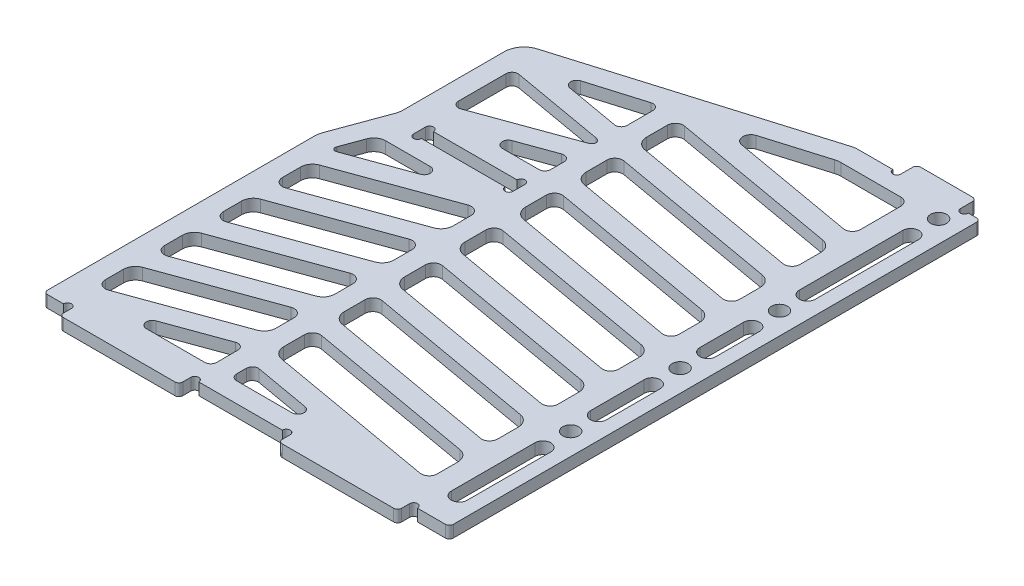
SolidWorks part; units mm, degrees
material "Thornel Mat VMA"
ref_plane "前视基准面" through (0, 0, 0) normal (0, 0, 1) x (1, 0, 0)
ref_plane "上视基准面" through (0, 0, 0) normal (0, 1, 0) x (1, 0, 0)
ref_plane "右视基准面" through (0, 0, 0) normal (1, 0, 0) x (0, 0, -1)
sketch "草图1" plane through (0, 0, 0) normal (0, 1, 0) x (1, 0, 0)
  line L0 (0, 0) -> (0, -3)
  line L1 (0, -3) -> (-30, -3)
  line L2 (-30, -3) -> (-30, 0)
  line L3 (-30, 0) -> (-55, 0)
  line L4 (-55, 0) -> (-55, -3)
  line L5 (-55, -3) -> (-85, -3)
  line L6 (-85, -3) -> (-85, 0)
  line L7 (-85, 0) -> (-92, 0)
  line L8 (-92, 0) -> (-92, 69)
  line L9 (-21.5, 133.5) -> (-10, 133.5)
  line L10 (10, 133.5) -> (10, 0)
  line L11 (10, 0) -> (0, 0)
  line L12 (5, 133.5) -> (10, 133.5)
  line L18 (5, 133.5) -> (5, 137.5)
  line L19 (5, 137.5) -> (-10, 137.5)
  line L20 (-10, 133.5) -> (-10, 137.5)
  line L22 (-86.5, 84) -> (-86.5, 114)
  line L23 (-86.5, 114) -> (-21.5, 133.5)
  line L24 (4.5, 121.5) -> (4.5, 95.5) construction
  line L25 (6.5, 121.5) -> (6.5, 95.5)
  line L26 (2.5, 121.5) -> (2.5, 95.5)
  line L27 (4.5, 81.5) -> (4.5, 70.5) construction
  line L28 (6.5, 81.5) -> (6.5, 70.5)
  line L29 (2.5, 81.5) -> (2.5, 70.5)
  line L31 (-80, 84) -> (-80, 81)
  line L33 (-80, 81) -> (-55, 81)
  line L34 (-55, 84) -> (-80, 84)
  line L37 (-55, 81) -> (-55, 84)
  line L38 (-92, 69) -> (-86.5, 84)
  line L39 (4.5, 56.5) -> (4.5, 43) construction
  line L40 (6.5, 56.5) -> (6.5, 43)
  line L41 (2.5, 56.5) -> (2.5, 43)
  line L42 (4.5, 29) -> (4.5, 8) construction
  line L43 (6.5, 29) -> (6.5, 8)
  line L44 (2.5, 29) -> (2.5, 8)
  circle A1 centre (4.5, 128.5) radius 2
  circle A5 centre (4.5, 36) radius 2
  circle A6 centre (4.5, 63.5) radius 2
  circle A7 centre (4.5, 88.5) radius 2
  arc A8 (6.5, 121.5) -> (2.5, 121.5) centre (4.5, 121.5) ccw
  arc A9 (2.5, 95.5) -> (6.5, 95.5) centre (4.5, 95.5) ccw
  arc A10 (6.5, 81.5) -> (2.5, 81.5) centre (4.5, 81.5) ccw
  arc A11 (2.5, 70.5) -> (6.5, 70.5) centre (4.5, 70.5) ccw
  arc A12 (6.5, 56.5) -> (2.5, 56.5) centre (4.5, 56.5) ccw
  arc A13 (2.5, 43) -> (6.5, 43) centre (4.5, 43) ccw
  arc A14 (6.5, 29) -> (2.5, 29) centre (4.5, 29) ccw
  arc A15 (2.5, 8) -> (6.5, 8) centre (4.5, 8) ccw
  point P28 (4.5, 108.5)
  point P41 (4.5, 76)
  point P46 (4.5, 49.75)
  point P55 (4.5, 18.5)
  point P63 (4.5, 123.5)
  point P64 (4.5, 93.5)
  point P68 (4.5, 83.5)
  point P69 (4.5, 68.5)
  point P70 (4.5, 58.5)
  point P71 (4.5, 41)
  point P72 (4.5, 31)
  point P73 (4.5, 6)
  dimension "D20" = 4
  dimension "D21" = 5
  dimension "D22" = 40
  dimension "D23" = 25
  dimension "D24" = 27.5
  dimension "D28" = 5
  dimension "D30" = 5
  dimension "D31" = 5
  dimension "D1" = 3
  dimension "D2" = 10
  dimension "D3" = 133.5
  dimension "D4" = 30
  dimension "D5" = 25
  dimension "D6" = 30
  dimension "D7" = 7
  dimension "D8" = 4
  dimension "D9" = 5
  dimension "D10" = 81
  dimension "D11" = 3
  dimension "D12" = 5.5
  dimension "D13" = 25
  dimension "D14" = 6.5
  dimension "D15" = 15
  dimension "D16" = 15
  dimension "D17" = 30
  dimension "D18" = 65
  dimension "D19" = 5.5
  dimension "D25" = 5
  dimension "D26" = 5
  dimension "D27" = 4
  dimension "D29" = 5
  dimension "D32" = 5
  dimension "D33" = 6
extrude "凸台-拉伸1" add sketch "草图1" along normal blind 3
sketch "草图3" plane through (0, 3, 0) normal (0, 1, 0) x (1, 0, 0)
  line L38 (-84.1078, 76) -> (-55, 76)
  line L39 (-81.5, 89) -> (-55, 89)
  line L40 (-55, 89) -> (-55, 118.2298)
  line L41 (-50, 119.7298) -> (-50, 5)
  line L42 (-55, 76) -> (-55, 5)
  line L43 (-80, 81) -> (-55, 81) construction
  line L44 (-55, 84) -> (-80, 84) construction
  line L45 (-55, 81) -> (-55, 84) construction
  line L46 (-55, 118.2298) -> (-81.5, 110.2798)
  line L47 (-50, 5) -> (-3, 5)
  line L48 (-3, 128.5) -> (-3, 5)
  line L49 (10, 0) -> (10, 133.5) construction
  line L57 (-5, 128.5) -> (-20.7662, 128.5)
  line L58 (-20.7662, 128.5) -> (-81.5, 110.2798)
  line L59 (-81.5, 110.2798) -> (-81.5, 83.1122)
  line L60 (-81.5, 83.1122) -> (-87, 68.1122)
  line L61 (-87, 68.1122) -> (-87, 5)
  line L62 (-87, 5) -> (-80, 5)
  line L63 (-80, 2) -> (-60, 2)
  line L64 (-60, 5) -> (-25, 5)
  line L65 (-25, 2) -> (-5, 2)
  line L66 (-5, 5) -> (5, 5)
  line L67 (5, 5) -> (5, 128.5)
  line L68 (0, 132.5) -> (-5, 132.5)
  line L69 (-3, 128.5) -> (-20.7662, 128.5)
  line L70 (-20.7662, 128.5) -> (-50, 119.7298)
  line L71 (-81.5, 110.2798) -> (-81.5, 89)
  line L72 (-84.1078, 76) -> (-87, 68.1122)
  line L73 (-87, 68.1122) -> (-87, 5)
  line L76 (-87, 5) -> (-55, 5)
  line L81 (-80, 5) -> (-80, 2)
  line L83 (-60, 2) -> (-60, 5)
  line L85 (-25, 5) -> (-25, 2)
  line L87 (-5, 2) -> (-5, 5)
  line L89 (5, 128.5) -> (0, 128.5)
  line L91 (0, 128.5) -> (0, 132.5)
  line L93 (-5, 132.5) -> (-5, 128.5)
  dimension "D2" = 5
  dimension "D3" = 5
  dimension "D4" = 5
  dimension "D5" = 13
  dimension "D1" = 5
extrude "切除-拉伸2" cut sketch "草图3" against normal through all
sketch "草图4" plane through (0, 3, 0) normal (0, 1, 0) x (1, 0, 0)
  line L0 (-52, 99.7371) -> (-81.5, 89)
  line L1 (-52, 77.0919) -> (-90, 63.261)
  line L2 (-53, 105.0528) -> (-81.5, 110.0781)
  line L3 (-81.5, 110.2798) -> (-81.5, 89) construction
  line L4 (0, 19.6771) -> (-53, 29.0224)
  line L5 (0, 110.9135) -> (-53, 120.2588)
  line L6 (0, 4.471) -> (-53, 13.8163)
  line L7 (-55, 89) -> (-55, 118.2298) construction
  line L8 (-52, 62.2537) -> (-90, 48.4228)
  line L9 (-50, 119.7298) -> (-50, 5) construction
  line L10 (0, 95.7074) -> (-53, 105.0528)
  line L11 (0, 80.5014) -> (-53, 89.8467)
  line L12 (0, 65.2953) -> (-53, 74.6406)
  line L13 (0, 50.0892) -> (-53, 59.4346)
  line L14 (0, 34.8832) -> (-53, 44.2285)
  line L15 (-52, 47.4154) -> (-90, 33.5846)
  line L16 (-52, 32.5772) -> (-90, 18.7463)
  line L17 (-52, 17.739) -> (-90, 3.9081)
  line L18 (-81.5, 110.0781) -> (-83.4696, 110.4254)
  line L19 (-87, 68.1122) -> (-87, 5) construction
  line L20 (-55, 5) -> (-55, 76) construction
  line L23 (-3, 5) -> (-3, 128.5) construction
  line L24 (-55, 76) -> (-84.1078, 76) construction
  line L25 (-3, 128.5) -> (-20.7662, 128.5) construction
  dimension "D1" = 3
  dimension "D4" = 3
  dimension "D5" = 3
  dimension "D6" = 20
  dimension "D7" = 3
  dimension "D8" = 10
  dimension "D9" = 3
  dimension "D10" = 2
  dimension "D2" = 8
  dimension "D3" = 5
extrude "拉伸-薄壁1" add sketch "草图4" against normal up to surface (3 mm away) thin up to face at (-25.3532, 0, -77.346) thin type mid plane wall 5
sketch "草图2" plane through (0, 3, 0) normal (0, 1, 0) x (1, 0, 0)
  line L0 (-55, 0) -> (-30, 0) construction
  line L1 (0, 0) -> (10, 0) construction
  line L2 (10, 133.5) -> (5, 133.5) construction
  line L3 (-10, 133.5) -> (-21.5, 133.5) construction
  line L4 (-55, 84) -> (-80, 84) construction
  line L8 (-92, 0) -> (-85, 0) construction
  line L9 (-80, 81) -> (-55, 81) construction
  circle A0 centre (-86, 0) radius 1
  circle A1 centre (-54, 0) radius 1
  circle A2 centre (-31, 0) radius 1
  circle A3 centre (1, 0) radius 1
  circle A4 centre (6, 133.5) radius 1
  circle A5 centre (-11, 133.5) radius 1
  circle A6 centre (-79, 84) radius 1
  circle A7 centre (-79, 81) radius 1
  circle A8 centre (-56, 84) radius 1
  circle A9 centre (-56, 81) radius 1
  dimension "D1" = 2
extrude "切除-拉伸1" cut sketch "草图2" against normal through all
fillet "圆角1" radius 1 9 edges at (10, 1.5, -133.5) (10, 1.5, 0) (-92, 1.5, 0) (0, 1.5, 3) (-30, 1.5, 3) (-55, 1.5, 3) (-85, 1.5, 3) (5, 1.5, -137.5) (-10, 1.5, -137.5)
fillet "圆角2" radius 5 5 edges at (-21.5, 1.5, -133.5) (-86.5, 1.5, -84) (-92, 1.5, -69) (-86.5, 1.5, -114) (-20.7662, 1.5, -128.5)
fillet "圆角3" radius 3 24 edges at (-87, 1.5, -68.1122) (-84.1078, 1.5, -76) (-87, 1.5, -61.6925) (-87, 1.5, -32.016) (-87, 1.5, -17.1778) (-87, 1.5, -46.8543) (-3, 1.5, -108.9039) (-3, 1.5, -93.6978) (-3, 1.5, -17.6675) (-3, 1.5, -78.4918) (-3, 1.5, -63.2857) (-3, 1.5, -48.0796) (-3, 1.5, -32.8736) (-50, 1.5, -31.032) (-50, 1.5, -46.2381) (-50, 1.5, -61.4441) (-50, 1.5, -76.6502) (-50, 1.5, -15.8259) (-50, 1.5, -91.8563) (-50, 1.5, -107.0623) (-55, 1.5, -48.984) (-55, 1.5, -19.3075) (-55, 1.5, -34.1457) (-55, 1.5, -63.8222)
fillet "圆角4" radius 1.5 18 edges at (-76.5941, 1.5, -111.7516) (-55, 1.5, -118.2298) (-55, 1.5, -102.8668) (-55, 1.5, -101.3057) (-55, 1.5, -95.9848) (-55, 1.5, -89) (-55, 1.5, -107.944) (-81.5, 1.5, -91.6604) (-81.5, 1.5, -107.5395) (-74.1905, 1.5, -89) (-50, 1.5, -5) (-50, 1.5, -10.7488) (-17.3969, 1.5, -5) (-55, 1.5, -5) (-55, 1.5, -13.9866) (-79.6905, 1.5, -5) (-62.3095, 1.5, -76) (-87, 1.5, -67.0134)
fillet "圆角5" radius 2 25 edges at (-3, 1.5, -22.7446) (-3, 1.5, -37.9507) (-3, 1.5, -53.1568) (-3, 1.5, -68.3628) (-3, 1.5, -128.5) (-3, 1.5, -113.981) (-44.6705, 1.5, -121.3287) (-3, 1.5, -7.5386) (-55, 1.5, -73.3396) (-55, 1.5, -43.6631) (-55, 1.5, -28.8248) (-3, 1.5, -83.5689) (-55, 1.5, -58.5013) (-50, 1.5, -117.1913) (-50, 1.5, -101.9852) (-3, 1.5, -98.775) (-50, 1.5, -25.9549) (-50, 1.5, -86.7791) (-50, 1.5, -71.5731) (-50, 1.5, -56.367) (-50, 1.5, -41.1609) (-87, 1.5, -37.3369) (-87, 1.5, -7.6604) (-87, 1.5, -22.4987) (-87, 1.5, -52.1752)
fillet "圆角6" radius 0.8 2 edges at (-87, 1.5, -67.5796) (-55.0473, 1.5, -101.9821)
